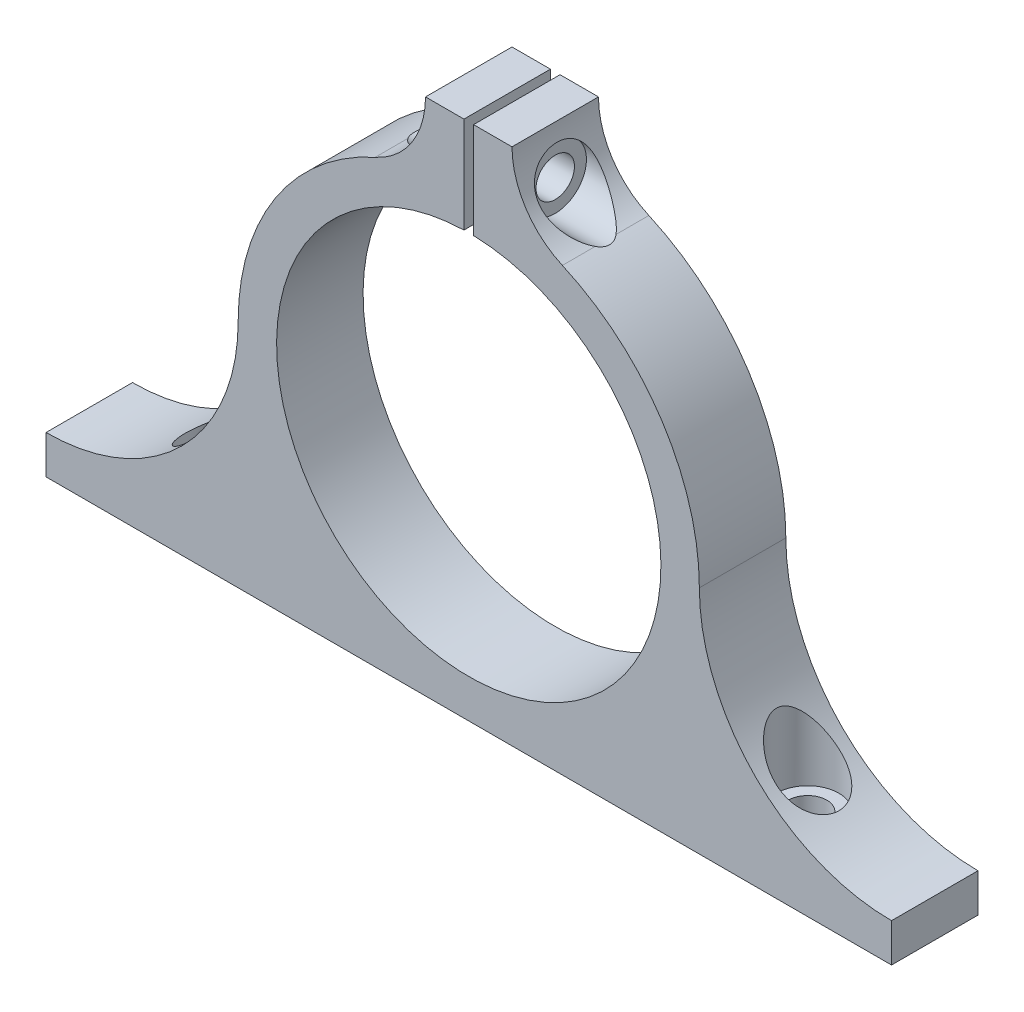
SolidWorks part; units mm, degrees
ref_plane "Front Plane" through (0, 0, 0) normal (0, 0, 1) x (1, 0, 0)
ref_plane "Top Plane" through (0, 0, 0) normal (0, 1, 0) x (1, 0, 0)
ref_plane "Right Plane" through (0, 0, 0) normal (1, 0, 0) x (0, 0, -1)
sketch "Sketch1" plane through (0, 0, 0) normal (0, 0, 1) x (1, 0, 0)
  line L0 (0, 0) -> (0, 48) construction
  line L1 (0, 0) -> (88, 0) construction
  line L2 (0, 0) -> (-88, 0) construction
  line L3 (88, -40) -> (88, -48)
  line L4 (88, -48) -> (-88, -48)
  line L5 (-88, -48) -> (-88, -40)
  line L6 (0, 48) -> (0, 60) construction
  line L7 (0, 60) -> (1, 60) construction
  line L8 (1, 60) -> (1, 39.9875)
  line L9 (1, 60) -> (9, 60)
  line L11 (0, 60) -> (-1, 60) construction
  line L12 (-1, 60) -> (-1, 39.9875)
  line L13 (-1, 60) -> (-9, 60)
  arc A0 (-1, 39.9875) -> (1, 39.9875) centre (0, 0) ccw
  arc A1 (48, 0) -> (19.4868, 43.8664) centre (0, 0) ccw
  arc A2 (-19.4868, 43.8664) -> (-48, 0) centre (0, 0) ccw
  arc A3 (9, 60) -> (19.4868, 43.8664) centre (26.6538, 60) ccw
  arc A4 (-88, -40) -> (-48, 0) centre (-88, 0) ccw
  arc A5 (48, 0) -> (88, -40) centre (88, 0) ccw
  arc A6 (-19.4868, 43.8664) -> (-9, 60) centre (-26.6538, 60) ccw
  dimension "D1" = 80
  dimension "D3" = 80
  dimension "D4" = 80
  dimension "D2" = 48
  dimension "D5" = 8
  dimension "D6" = 12
  dimension "D7" = 1
  dimension "D8" = 8
  dimension "D9" = 1
  dimension "D10" = 8
extrude "Boss-Extrude1" add sketch "Sketch1" along normal blind 18
sketch "Sketch3" plane through (0, 0, 18) normal (0, 0, 1) x (1, 0, 0)
  line L0 (-61.5425, -48) -> (-61.5425, -30) construction
  line L1 (-88, -48) -> (88, -48) construction
  line L2 (61.5425, -48) -> (61.5425, -30) construction
  arc A0 (-88, -40) -> (-48, 0) centre (-88, 0) ccw construction
  arc A1 (48, 0) -> (88, -40) centre (88, 0) ccw construction
  dimension "D1" = 18
  dimension "D2" = 18
sketch "Sketch4" plane through (0, -48, 0) normal (0, -1, 0) x (1, 0, 0)
  line L0 (-88, 9) -> (88, 9) construction
  line L1 (-88, 18) -> (-88, 0) construction
  line L2 (88, 18) -> (88, 0) construction
  line L3 (61.5425, 9) -> (61.5425, 18) construction
  line L4 (-61.5425, 18) -> (-61.5425, 9) construction
  circle A0 centre (-61.5425, 9) radius 4
  circle A1 centre (61.5425, 9) radius 4
  dimension "D1" = 8
  dimension "D2" = 8
extrude "Cut-Extrude2" cut sketch "Sketch4" against normal through all
sketch "Sketch5" plane through (0, 0, 0) normal (0, 0, -1) x (-1, 0, 0)
  line L0 (-61.5425, -48) -> (-61.5425, -38) construction
  line L1 (-61.5425, -48) -> (-61.5425, -30) construction
  line L2 (-61.5425, -38) -> (61.5425, -38) construction
  line L3 (61.5425, -48) -> (61.5425, -30) construction
  dimension "D1" = 10
ref_plane "Plane1" through (0, -38, 0) normal (0, 1, 0) x (1, 0, 0)
sketch "Sketch6" plane through (0, -38, 0) normal (0, 1, 0) x (1, 0, 0)
  circle A0 centre (-61.5425, -9) radius 6.5
  circle A1 centre (61.5425, -9) radius 6.5
  dimension "D1" = 13
  dimension "D2" = 13
extrude "Cut-Extrude3" cut sketch "Sketch6" along normal through all
sketch "Sketch7" plane through (1, 0, 0) normal (-1, 0, 0) x (0, 0, 1)
  line L0 (9, 39.9875) -> (9, 60) construction
  line L1 (18, 39.9875) -> (0, 39.9875) construction
  line L2 (18, 60) -> (0, 60) construction
  circle A0 centre (9, 49.9937) radius 4
  dimension "D1" = 8
extrude "Cut-Extrude4" cut sketch "Sketch7" against normal through all and the other way through all
ref_plane "Plane2" through (-9, 0, 0) normal (1, 0, 0) x (0, 0, -1)
sketch "Sketch8" plane through (-9, 0, 0) normal (1, 0, 0) x (0, 0, -1)
  circle A0 centre (-9, 49.9937) radius 6.5
  dimension "D1" = 13
extrude "Cut-Extrude5" cut sketch "Sketch8" against normal blind 18
ref_plane "Plane3" through (9, 0, 0) normal (-1, 0, 0) x (0, 0, 1)
sketch "Sketch10" plane through (9, 0, 0) normal (-1, 0, 0) x (0, 0, 1)
  circle A0 centre (9, 49.9937) radius 6.5
  dimension "D1" = 13
extrude "Cut-Extrude6" cut sketch "Sketch10" against normal blind 18
